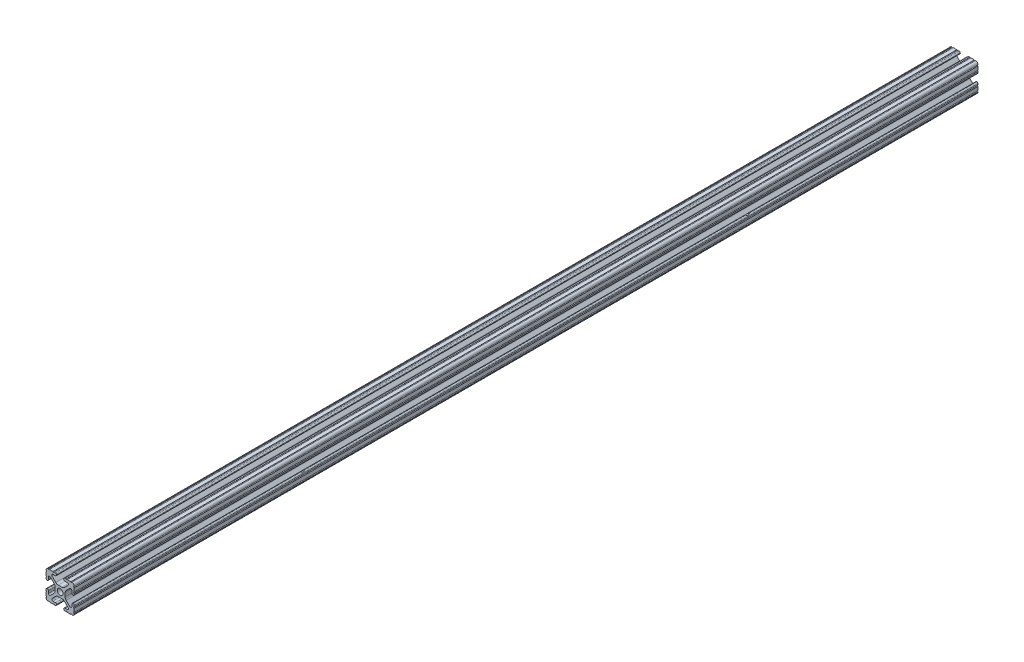
SolidWorks part; units mm, degrees
ref_plane "Front Plane" through (0, 0, 0) normal (0, 0, 1) x (1, 0, 0)
ref_plane "Top Plane" through (0, 0, 0) normal (0, 1, 0) x (1, 0, 0)
ref_plane "Right Plane" through (0, 0, 0) normal (1, 0, 0) x (0, 0, -1)
sketch "Sketch1" plane through (0, 0, 0) normal (0, 0, 1) x (1, 0, 0)
  line L88 (-7.1797, -8.6452) -> (-3.9523, -5.4237)
  line L89 (-1.7093, -4.4958) -> (1.7093, -4.4958)
  line L90 (3.9523, -5.4237) -> (7.1797, -8.6452)
  line L91 (6.4164, -10.4902) -> (4.2875, -10.4902)
  line L92 (3.2385, -11.5392) -> (3.2385, -11.651)
  line L93 (4.2875, -12.7) -> (5.3171, -12.7)
  line L94 (6.3331, -12.7) -> (9.5504, -12.7)
  line L95 (12.7, -9.5504) -> (12.7, -6.3331)
  line L96 (12.7, -5.3171) -> (12.7, -4.2875)
  line L97 (11.651, -3.2385) -> (11.5392, -3.2385)
  line L98 (10.4902, -4.2875) -> (10.4902, -6.4021)
  line L99 (8.7371, -7.1294) -> (5.441, -3.8408)
  line L100 (4.5085, -1.5932) -> (4.5085, 1.5932)
  line L101 (5.441, 3.8408) -> (8.7371, 7.1294)
  line L102 (10.4902, 6.4021) -> (10.4902, 4.2875)
  line L103 (11.5392, 3.2385) -> (11.651, 3.2385)
  line L104 (12.7, 4.2875) -> (12.7, 5.3171)
  line L105 (12.7, 6.3331) -> (12.7, 9.5504)
  line L106 (9.5504, 12.7) -> (6.3331, 12.7)
  line L107 (5.3171, 12.7) -> (4.2875, 12.7)
  line L108 (3.2385, 11.651) -> (3.2385, 11.5392)
  line L109 (4.2875, 10.4902) -> (6.4768, 10.4902)
  line L110 (7.207, 8.7244) -> (3.8983, 5.4232)
  line L111 (1.6558, 4.4958) -> (-1.6558, 4.4958)
  line L112 (-3.8983, 5.4232) -> (-7.207, 8.7244)
  line L113 (-6.4768, 10.4902) -> (-4.2875, 10.4902)
  line L114 (-3.2385, 11.5392) -> (-3.2385, 11.651)
  line L115 (-4.2875, 12.7) -> (-5.3171, 12.7)
  line L116 (-6.3331, 12.7) -> (-9.5504, 12.7)
  line L117 (-12.7, 9.5504) -> (-12.7, 6.3331)
  line L118 (-12.7, 5.3171) -> (-12.7, 4.2875)
  line L119 (-11.651, 3.2385) -> (-11.5392, 3.2385)
  line L120 (-10.4902, 4.2875) -> (-10.4902, 6.4021)
  line L121 (-8.7371, 7.1294) -> (-5.441, 3.8408)
  line L122 (-4.5085, 1.5932) -> (-4.5085, -1.5932)
  line L123 (-5.441, -3.8408) -> (-8.7371, -7.1294)
  line L124 (-10.4902, -6.4021) -> (-10.4902, -4.2875)
  line L125 (-11.5392, -3.2385) -> (-11.651, -3.2385)
  line L126 (-12.7, -4.2875) -> (-12.7, -5.3171)
  line L127 (-12.7, -6.3331) -> (-12.7, -9.5504)
  line L128 (-9.5504, -12.7) -> (-6.3331, -12.7)
  line L129 (-5.3171, -12.7) -> (-4.2875, -12.7)
  line L130 (-3.2385, -11.651) -> (-3.2385, -11.5392)
  line L131 (-4.2875, -10.4902) -> (-6.4164, -10.4902)
  circle A1 centre (0, 0) radius 2.6035
  arc A104 (-7.1797, -8.6452) -> (-6.4164, -10.4902) centre (-6.4164, -9.4098) ccw
  arc A105 (-1.7093, -4.4958) -> (-3.9523, -5.4237) centre (-1.7093, -7.6708) ccw
  arc A106 (3.9523, -5.4237) -> (1.7093, -4.4958) centre (1.7093, -7.6708) ccw
  arc A107 (6.4164, -10.4902) -> (7.1797, -8.6452) centre (6.4164, -9.4098) ccw
  arc A108 (4.2875, -10.4902) -> (3.2385, -11.5392) centre (4.2875, -11.5392) ccw
  arc A109 (3.2385, -11.651) -> (4.2875, -12.7) centre (4.2875, -11.651) ccw
  arc A110 (6.3331, -12.7) -> (5.3171, -12.7) centre (5.8251, -12.7) ccw
  arc A111 (10.5664, -12.6998) -> (9.5504, -12.7) centre (10.0584, -12.7) ccw
  arc A112 (10.5664, -12.6998) -> (12.6998, -10.5664) centre (10.5918, -10.5918) ccw
  arc A113 (12.7, -9.5504) -> (12.6998, -10.5664) centre (12.7, -10.0584) ccw
  arc A114 (12.7, -5.3171) -> (12.7, -6.3331) centre (12.7, -5.8251) ccw
  arc A115 (12.7, -4.2875) -> (11.651, -3.2385) centre (11.651, -4.2875) ccw
  arc A116 (11.5392, -3.2385) -> (10.4902, -4.2875) centre (11.5392, -4.2875) ccw
  arc A117 (8.7371, -7.1294) -> (10.4902, -6.4021) centre (9.4628, -6.4021) ccw
  arc A118 (4.5085, -1.5932) -> (5.441, -3.8408) centre (7.6835, -1.5932) ccw
  arc A119 (5.441, 3.8408) -> (4.5085, 1.5932) centre (7.6835, 1.5932) ccw
  arc A120 (10.4902, 6.4021) -> (8.7371, 7.1294) centre (9.4628, 6.4021) ccw
  arc A121 (10.4902, 4.2875) -> (11.5392, 3.2385) centre (11.5392, 4.2875) ccw
  arc A122 (11.651, 3.2385) -> (12.7, 4.2875) centre (11.651, 4.2875) ccw
  arc A123 (12.7, 6.3331) -> (12.7, 5.3171) centre (12.7, 5.8251) ccw
  arc A124 (12.6998, 10.5664) -> (12.7, 9.5504) centre (12.7, 10.0584) ccw
  arc A125 (12.6998, 10.5664) -> (10.5664, 12.6998) centre (10.5918, 10.5918) ccw
  arc A126 (9.5504, 12.7) -> (10.5664, 12.6998) centre (10.0584, 12.7) ccw
  arc A127 (5.3171, 12.7) -> (6.3331, 12.7) centre (5.8251, 12.7) ccw
  arc A128 (4.2875, 12.7) -> (3.2385, 11.651) centre (4.2875, 11.651) ccw
  arc A129 (3.2385, 11.5392) -> (4.2875, 10.4902) centre (4.2875, 11.5392) ccw
  arc A130 (7.207, 8.7244) -> (6.4768, 10.4902) centre (6.4768, 9.4563) ccw
  arc A131 (1.6558, 4.4958) -> (3.8983, 5.4232) centre (1.6558, 7.6708) ccw
  arc A132 (-3.8983, 5.4232) -> (-1.6558, 4.4958) centre (-1.6558, 7.6708) ccw
  arc A133 (-6.4768, 10.4902) -> (-7.207, 8.7244) centre (-6.4768, 9.4563) ccw
  arc A134 (-4.2875, 10.4902) -> (-3.2385, 11.5392) centre (-4.2875, 11.5392) ccw
  arc A135 (-3.2385, 11.651) -> (-4.2875, 12.7) centre (-4.2875, 11.651) ccw
  arc A136 (-6.3331, 12.7) -> (-5.3171, 12.7) centre (-5.8251, 12.7) ccw
  arc A137 (-10.5664, 12.6998) -> (-9.5504, 12.7) centre (-10.0584, 12.7) ccw
  arc A138 (-10.5664, 12.6998) -> (-12.6998, 10.5664) centre (-10.5918, 10.5918) ccw
  arc A139 (-12.7, 9.5504) -> (-12.6998, 10.5664) centre (-12.7, 10.0584) ccw
  arc A140 (-12.7, 5.3171) -> (-12.7, 6.3331) centre (-12.7, 5.8251) ccw
  arc A141 (-12.7, 4.2875) -> (-11.651, 3.2385) centre (-11.651, 4.2875) ccw
  arc A142 (-11.5392, 3.2385) -> (-10.4902, 4.2875) centre (-11.5392, 4.2875) ccw
  arc A143 (-8.7371, 7.1294) -> (-10.4902, 6.4021) centre (-9.4628, 6.4021) ccw
  arc A144 (-4.5085, 1.5932) -> (-5.441, 3.8408) centre (-7.6835, 1.5932) ccw
  arc A145 (-5.441, -3.8408) -> (-4.5085, -1.5932) centre (-7.6835, -1.5932) ccw
  arc A146 (-10.4902, -6.4021) -> (-8.7371, -7.1294) centre (-9.4628, -6.4021) ccw
  arc A147 (-10.4902, -4.2875) -> (-11.5392, -3.2385) centre (-11.5392, -4.2875) ccw
  arc A148 (-11.651, -3.2385) -> (-12.7, -4.2875) centre (-11.651, -4.2875) ccw
  arc A149 (-12.7, -6.3331) -> (-12.7, -5.3171) centre (-12.7, -5.8251) ccw
  arc A150 (-12.6998, -10.5664) -> (-12.7, -9.5504) centre (-12.7, -10.0584) ccw
  arc A151 (-12.6998, -10.5664) -> (-10.5664, -12.6998) centre (-10.5918, -10.5918) ccw
  arc A152 (-9.5504, -12.7) -> (-10.5664, -12.6998) centre (-10.0584, -12.7) ccw
  arc A153 (-5.3171, -12.7) -> (-6.3331, -12.7) centre (-5.8251, -12.7) ccw
  arc A154 (-4.2875, -12.7) -> (-3.2385, -11.651) centre (-4.2875, -11.651) ccw
  arc A155 (-3.2385, -11.5392) -> (-4.2875, -10.4902) centre (-4.2875, -11.5392) ccw
extrude "Boss-Extrude1" add sketch "Sketch1" along normal mid plane 812.8
sketch "Sketch2" plane through (0, 4.4958, 0) normal (0, 1, 0) x (1, 0, 0)
  circle A0 centre (0.2407, 250) radius 3.175
  circle A1 centre (0, -250) radius 3.175
  dimension "D1" = 6.35
  dimension "D2" = 250
  dimension "D3" = 6.35
  dimension "D4" = 250
extrude "Cut-Extrude1" cut sketch "Sketch2" against normal through all both and the other way through all contours A1 | A0
sketch "Sketch3" plane through (4.5085, 0, 0) normal (1, 0, 0) x (0, 0, -1)
  line L0 (0, 0) -> (0, -131.3157) construction
  circle A0 centre (200, 0) radius 3.5
  circle A1 centre (-200, 0) radius 3.5
  point P6 (0, 0)
  point P7 (0, 0)
  point P9 (0, 0)
  dimension "D1" = 7
  dimension "D2" = 200
extrude "Cut-Extrude2" cut sketch "Sketch3" against normal through all both and the other way through all
